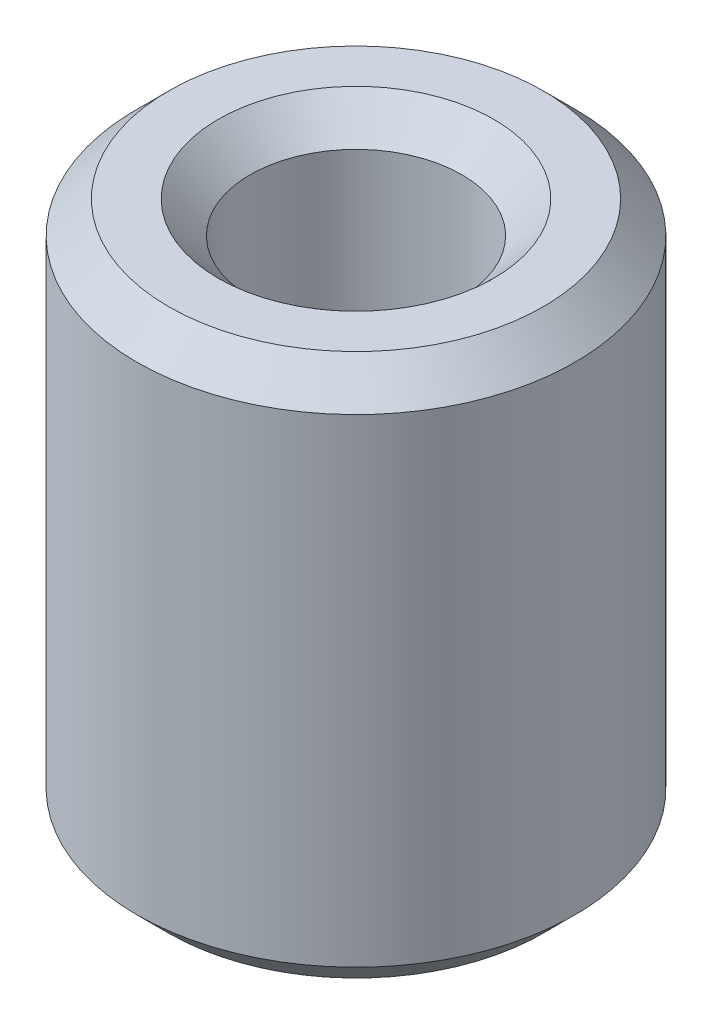
SolidWorks part; units mm, degrees
ref_plane "Front Plane" through (0, 0, 0) normal (0, 0, 1) x (1, 0, 0)
ref_plane "Top Plane" through (0, 0, 0) normal (0, 1, 0) x (1, 0, 0)
ref_plane "Right Plane" through (0, 0, 0) normal (1, 0, 0) x (0, 0, -1)
sketch "Sketch1" plane through (0, 0, 0) normal (0, 1, 0) x (1, 0, 0)
  circle A0 centre (0, 0) radius 5
  dimension "SLEEVE_OD" = 10
extrude "Boss-Extrude1" add sketch "Sketch1" along normal blind 12.3809
sketch "Sketch2" plane through (0, 0, 0) normal (0, 1, 0) x (1, 0, 0)
  circle A0 centre (0, 0) radius 2.414
  dimension "BORE_D" = 4.8281
extrude "Cut-Extrude1" cut sketch "Sketch2" along normal through all
chamfer "Chamfer1" distance 0.7295 angle 45 4 edges at (0, 12.3809, 2.414) (0, 0, 2.414) (0, 0, 5) (0, 12.3809, 5)
